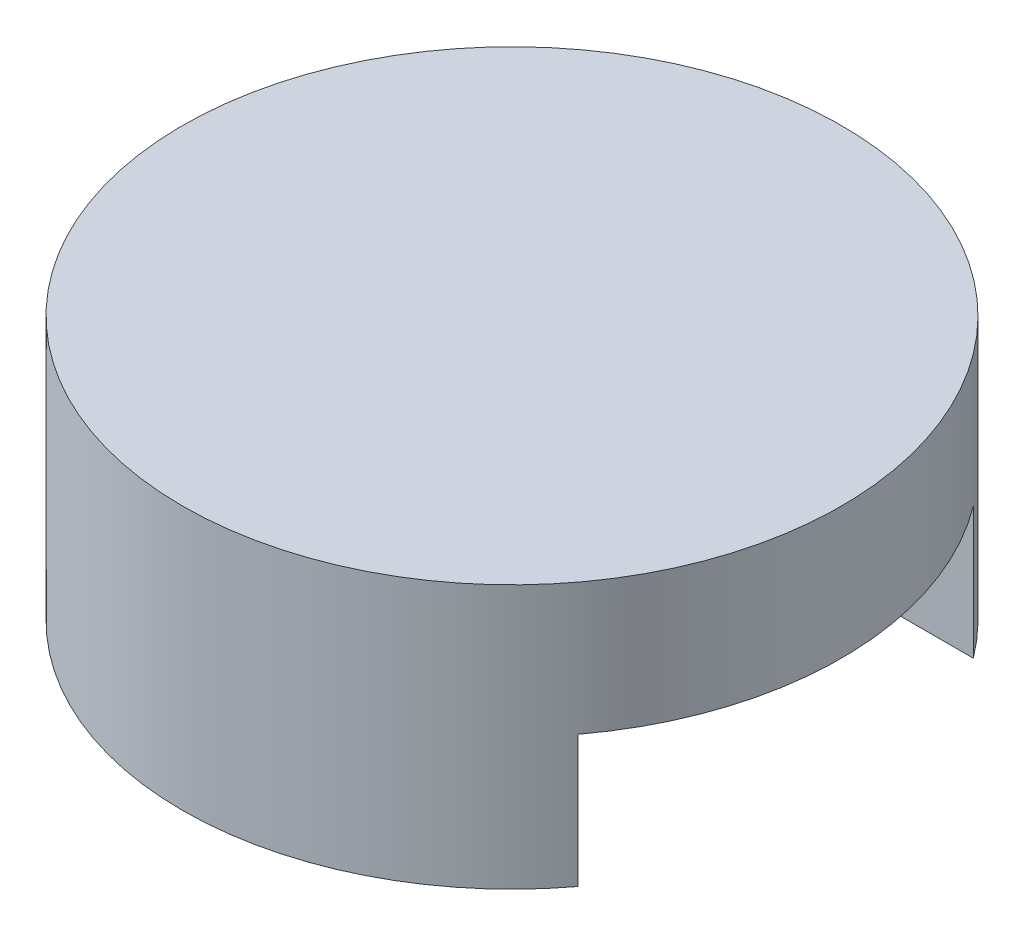
SolidWorks part; units mm, degrees
ref_plane "Front Plane" through (0, 0, 0) normal (0, 0, 1) x (1, 0, 0)
ref_plane "Top Plane" through (0, 0, 0) normal (0, 1, 0) x (1, 0, 0)
ref_plane "Right Plane" through (0, 0, 0) normal (1, 0, 0) x (0, 0, -1)
sketch "Sketch1" plane through (0, 0, 0) normal (0, 1, 0) x (1, 0, 0)
  circle A0 centre (0, 0) radius 15.875
  dimension "D1" = 31.75
extrude "Boss-Extrude1" add sketch "Sketch1" along normal blind 12.7
sketch "Sketch2" plane through (0, 0, 0) normal (1, 0, 0) x (0, 0, -1)
  line L0 (0, 0) -> (0, 50000) construction
  line L6 (-9.525, 0) -> (9.525, 0)
  line L7 (-15.875, 0) -> (15.875, 0) construction
  line L8 (9.525, 0) -> (9.525, 6.35)
  line L9 (9.525, 6.35) -> (-9.525, 6.35)
  line L10 (-9.525, 0) -> (-9.525, 6.35)
  point P0 (0, 0)
  point P11 (0, 0)
  point P12 (0, 6.35)
  dimension "D1" = 6.35
  dimension "D2" = 19.05
extrude "Cut-Extrude1" cut sketch "Sketch2" against normal through all and the other way through all
